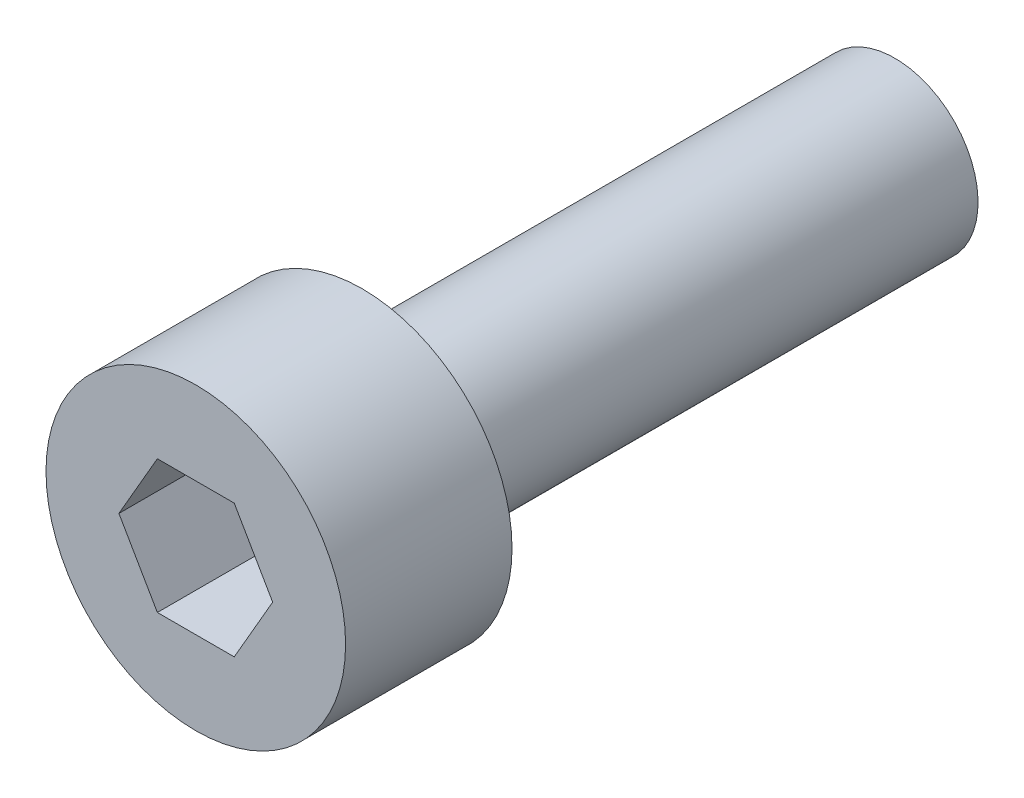
SolidWorks part; units mm, degrees
material "AISI 304"
ref_plane "Front Plane" through (0, 0, 0) normal (0, 0, 1) x (1, 0, 0)
ref_plane "Top Plane" through (0, 0, 0) normal (0, 1, 0) x (1, 0, 0)
ref_plane "Right Plane" through (0, 0, 0) normal (1, 0, 0) x (0, 0, -1)
ref_axis "Axis1" through (0, 0, -52.8182) along (0, 0, 1)
ref_axis "Axis2" through (0, -15.5981, 0) along (0, 1, 0)
ref_axis "Axis3" through (-12.2581, 0, 0) along (1, 0, 0)
sketch "Sketch1" plane through (0, 0, 0) normal (1, 0, 0) x (0, 0, -1)
  line L0 (-2.5, 0) -> (-2.5, 2.25)
  line L1 (-2.5, 2.25) -> (0, 2.25)
  line L2 (0, 2.25) -> (0, 1.25)
  line L3 (0, 1.25) -> (8, 1.25)
  line L4 (8, 1.25) -> (8, 0)
  line L5 (8, 0) -> (-2.5, 0)
  line L6 (-5.5849, 0) -> (13.8966, 0) construction
  dimension "D1" = 2.5
  dimension "D2" = 4.5
  dimension "D3" = 2.5
  dimension "Length" = 8
revolve "Revolve1" add sketch "Sketch1" angle 360 about L6
cosmetic thread "Cosmetic Thread1" parameters "D1"=8, "D2"=1.993
sketch "Sketch2" plane through (0, 0, 2.5) normal (0, 0, 1) x (1, 0, 0)
  line L1 (0.5774, -1) -> (1.1547, 0)
  line L2 (1.1547, 0) -> (0.5774, 1)
  line L3 (0.5774, 1) -> (-0.5774, 1)
  line L4 (-0.5774, 1) -> (-1.1547, 0)
  line L5 (-1.1547, 0) -> (-0.5774, -1)
  line L6 (-0.5774, -1) -> (0.5774, -1)
  circle A0 centre (0, 0) radius 1 construction
  dimension "D1" = 2
extrude "Cut-Extrude1" cut sketch "Sketch2" against normal blind 1.5
